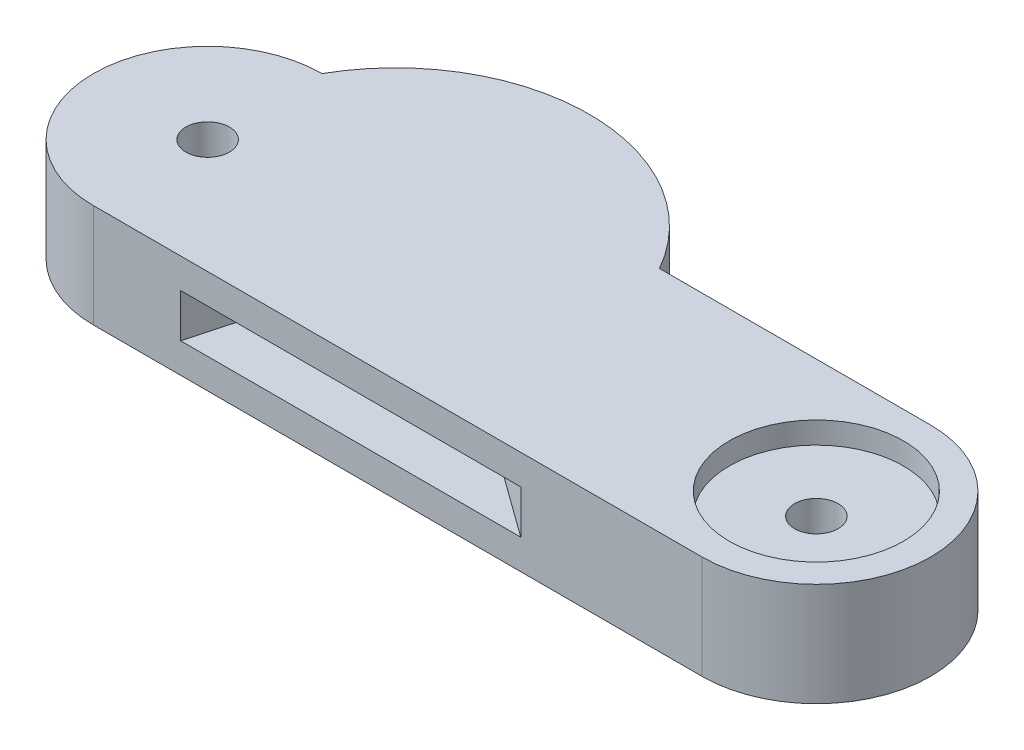
SolidWorks part; units mm, degrees
ref_plane "Front Plane" through (0, 0, 0) normal (0, 0, 1) x (1, 0, 0)
ref_plane "Top Plane" through (0, 0, 0) normal (0, 1, 0) x (1, 0, 0)
ref_plane "Right Plane" through (0, 0, 0) normal (1, 0, 0) x (0, 0, -1)
sketch "Sketch1" plane through (0, 0, 0) normal (0, 1, 0) x (1, 0, 0)
  line L0 (0, -10.5004) -> (-55.9305, -10.5004)
  line L1 (0, 10.5004) -> (-55.9305, 10.5004)
  line L5 (0, 11.5004) -> (-55.9305, 11.5004) construction
  line L6 (0, -11.5004) -> (-55.9305, -11.5004) construction
  circle A0 centre (0, 0) radius 2
  arc A1 (0, -10.5004) -> (0, 10.5004) centre (0, 0) ccw
  arc A2 (-55.9305, 10.5004) -> (-55.9305, -10.5004) centre (-55.9305, 0) ccw
  circle A3 centre (-55.9305, 0) radius 2
  arc A7 (0, -11.5004) -> (0, 11.5004) centre (0, 0) ccw construction
  arc A8 (-55.9305, 11.5004) -> (-55.9305, -11.5004) centre (-55.9305, 0) ccw construction
  arc A9 (-67.0955, -6.7172) -> (-54.5067, -17.0148) centre (-55.6523, -5.5716) ccw construction
  arc A10 (-55.9305, 10.5004) -> (-55.9305, -10.5004) centre (-55.9305, 0) ccw construction
  circle A11 centre (0, 0) radius 67.4309 construction
  arc A12 (-60.661, 29.4479) -> (-67.0955, -6.7172) centre (0, 0) ccw construction
  dimension "D1" = 4
  dimension "D2" = 1
  dimension "D3" = 4
extrude "Boss-Extrude1" add sketch "Sketch1" along normal mid plane 9.5
sketch "Sketch3" plane through (0, 0, 0) normal (0, 1, 0) x (1, 0, 0)
  line L0 (0, 0) -> (-47.1525, -15.3208) construction
  line L1 (0, 0) -> (24.7895, -42.9367) construction
  line L2 (0, 0) -> (-55.9305, 0) construction
  line L3 (24.7895, -42.9367) -> (-41.5934, 5.0595) construction
  line L4 (-41.5934, 5.0595) -> (-47.1525, -15.3208) construction
  line L5 (-41.5934, 5.0595) -> (-37.6461, 19.5308) construction
  line L6 (-41.5934, 5.0595) -> (-53.749, 13.8482) construction
  line L7 (22.8477, -44.0007) -> (-38.0092, 0) construction
  line L8 (-35.7518, 18.8753) -> (-39.2995, 5.869)
  line L9 (-43.8873, 4.25) -> (-54.8123, 12.149)
  line L11 (26.6452, -41.8104) -> (-39.2995, 5.869)
  line L12 (-39.6108, 19.9279) -> (-42.7627, 8.3729) construction
  line L13 (-42.7627, 8.3729) -> (-52.4686, 15.3905) construction
  line L14 (-40.9004, 0) -> (-45.9674, -18.5763) construction
  line L15 (-43.8873, 4.25) -> (-48.2065, -11.585)
  line L18 (-40.4216, 6.6802) -> (-50.8477, 14.2185) construction
  line L20 (-41.5934, 5.0595) -> (-52.0196, 12.5978) construction
  line L21 (-42.7652, 3.4387) -> (-53.1914, 10.977) construction
  line L23 (-43.5229, 5.5858) -> (-49.082, -14.7945) construction
  line L26 (-39.6639, 4.5332) -> (-45.223, -15.8471) construction
  line L27 (25.9613, -41.316) -> (-40.4216, 6.6802) construction
  line L28 (23.6177, -44.5574) -> (-42.7652, 3.4387) construction
  arc A1 (-48.2065, -11.585) -> (26.6452, -41.8104) centre (0, 0) ccw
  arc A4 (-55.9305, 10.5004) -> (-55.9305, -10.5004) centre (-55.9305, 0) ccw construction
  arc A7 (-35.7518, 18.8753) -> (-54.8123, 12.149) centre (-41.5934, 5.0595) ccw
  dimension "D1" = 99.1581
  dimension "D3" = 120
  dimension "D6" = 30
  dimension "D2" = 18
  dimension "D4" = 2
  dimension "D5" = 2
extrude "Cut-Extrude1" cut sketch "Sketch3" against normal mid plane 4
sketch "Sketch5" plane through (0, 0, 0) normal (0, 1, 0) x (1, 0, 0)
  line L0 (-40.4241, 1.7461) -> (-52.5322, 10.5004) construction
  line L1 (-40.4241, 1.7461) -> (-35.7382, 18.9254) construction
  line L2 (-52.5322, 10.5004) -> (-43.8873, 4.25) construction
  line L3 (-39.2995, 5.869) -> (-38.0362, 10.5004) construction
  line L4 (-55.9305, 10.5004) -> (-24.9177, 10.5004)
  line L5 (0, 10.5004) -> (-55.9305, 10.5004) construction
  circle A0 centre (-40.4241, 1.7461) radius 17.807
extrude "Boss-Extrude2" add sketch "Sketch5" along normal up to surface and the other way up to surface contours A0 region at (-40.4241, 0, -14.2141) up to face at (0, 4.75, 2) other way up to face at (-27.9653, -4.75, 0)
sketch "Sketch6" plane through (0, 0, 0) normal (0, 1, 0) x (1, 0, 0)
  line L0 (-39.2995, 5.869) -> (-16.6593, -10.5004)
  line L1 (-47.9107, -10.5004) -> (-43.8873, 4.25)
  line L2 (-43.8873, 4.25) -> (-54.8544, 12.1794)
  line L3 (-39.2995, 5.869) -> (-35.7382, 18.9254)
  line L4 (-16.6593, -10.5004) -> (-39.2995, 5.869) construction
  line L5 (-43.8873, 4.25) -> (-47.9107, -10.5004) construction
  line L6 (-52.5322, 10.5004) -> (-43.8873, 4.25) construction
  line L7 (-39.2995, 5.869) -> (-38.0362, 10.5004) construction
  line L8 (-55.9305, -10.5004) -> (0, -10.5004) construction
  line L9 (-16.6593, -10.5004) -> (-47.9107, -10.5004)
  arc A0 (-24.9177, 10.5004) -> (-55.9305, 10.5004) centre (-40.4241, 1.7461) ccw construction
  arc A1 (-35.7382, 18.9254) -> (-54.8544, 12.1794) centre (-40.4241, 1.7461) ccw
extrude "Cut-Extrude2" cut sketch "Sketch6" against normal mid plane 4
sketch "Sketch7" plane through (0, 4.75, 0) normal (0, 1, 0) x (1, 0, 0)
  circle A0 centre (0, 0) radius 8
  dimension "D1" = 16
extrude "Cut-Extrude3" cut sketch "Sketch7" against normal blind 2
ref_plane "Plane1" through (0, 0, 0) normal (0, 1, 0) x (1, 0, 0)
